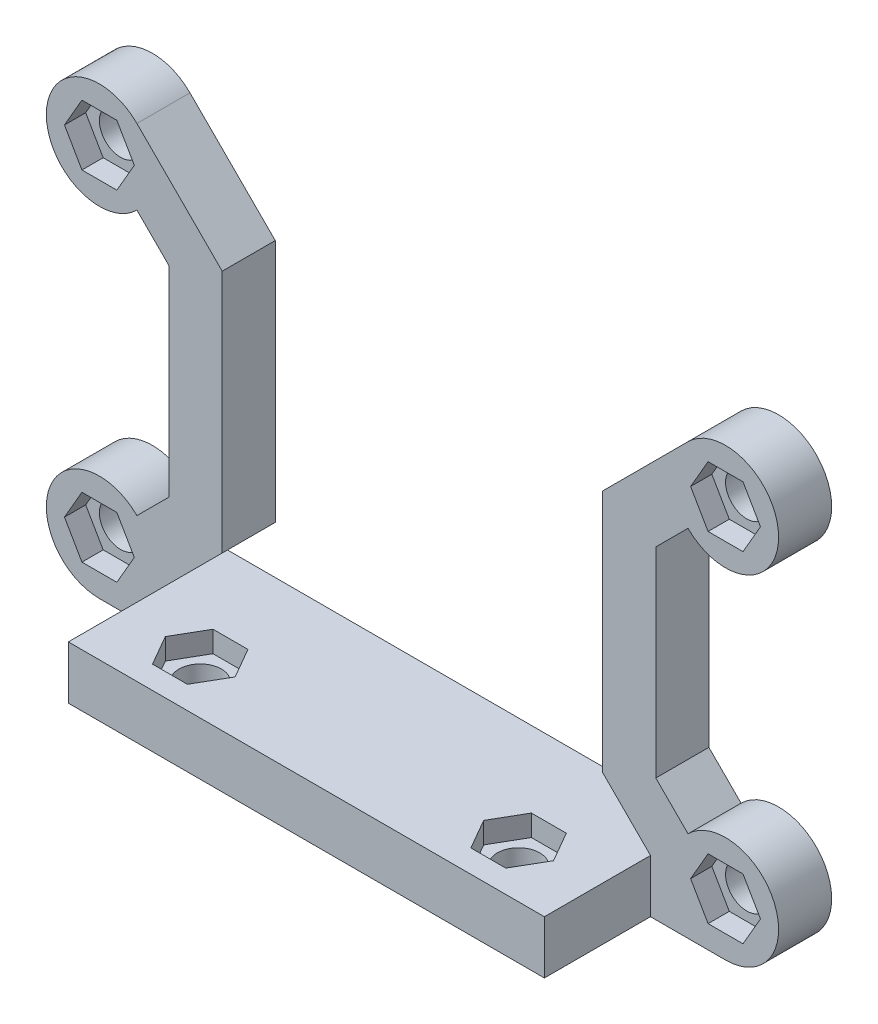
SolidWorks part; units mm, degrees
ref_plane "Plan de face" through (0, 0, 0) normal (0, 0, 1) x (1, 0, 0)
ref_plane "Plan de dessus" through (0, 0, 0) normal (0, 1, 0) x (1, 0, 0)
ref_plane "Plan de droite" through (0, 0, 0) normal (1, 0, 0) x (0, 0, -1)
sketch "Esquisse1" plane through (0, 0, 0) normal (0, 0, 1) x (1, 0, 0)
  line L0 (0, 32) -> (0, 0) construction
  line L1 (6.5711, 25.4289) -> (6.5711, 6.5711)
  line L2 (11.5711, 27.5) -> (11.5711, 4.5)
  line L3 (11.5711, 4.5) -> (3.5355, -3.5355)
  line L4 (6.5711, 6.5711) -> (3.5355, 3.5355)
  line L5 (6.5711, 25.4289) -> (3.5355, 28.4645)
  line L6 (11.5711, 27.5) -> (3.5355, 35.5355)
  line L7 (3.5355, 35.5355) -> (3.5355, 28.4645) construction
  line L8 (3.5355, 3.5355) -> (3.5355, -3.5355) construction
  line L9 (0, 32) -> (29.5, 32) construction
  line L10 (29.5, 32) -> (29.5, 0) construction
  line L11 (0, 0) -> (29.5, 0) construction
  line L12 (52.4289, 6.5711) -> (55.4645, 3.5355)
  line L13 (52.4289, 25.4289) -> (52.4289, 6.5711)
  line L14 (52.4289, 25.4289) -> (55.4645, 28.4645)
  line L15 (47.4289, 27.5) -> (55.4645, 35.5355)
  line L16 (47.4289, 27.5) -> (47.4289, 4.5)
  line L17 (47.4289, 4.5) -> (55.4645, -3.5355)
  line L18 (0, -5) -> (59, -5)
  line L19 (7.0711, 0) -> (51.9289, 0)
  circle A0 centre (0, 32) radius 2
  circle A1 centre (0, 32) radius 5 construction
  circle A2 centre (0, 0) radius 5 construction
  circle A3 centre (0, 0) radius 2
  arc A4 (3.5355, 35.5355) -> (3.5355, 28.4645) centre (0, 32) ccw
  arc A5 (3.5355, 3.5355) -> (3.5355, -3.5355) centre (0, 0) ccw
  circle A6 centre (59, 32) radius 2
  circle A7 centre (59, 0) radius 2
  arc A8 (55.4645, 35.5355) -> (55.4645, 28.4645) centre (59, 32) cw
  arc A9 (55.4645, 3.5355) -> (55.4645, -3.5355) centre (59, 0) cw
  dimension "D1" = 4
  dimension "D2" = 10
  dimension "D3" = 32
  dimension "D4" = 5
  dimension "D5" = 5
  dimension "D6" = 5
  dimension "D7" = 135
  dimension "D8" = 135
  dimension "D9" = 23
  dimension "D10" = 29.5
  dimension "D11" = 5
extrude "Boss.-Extru.1" add sketch "Esquisse1" along normal blind 5 contours L18 A9 L17 L19 L3 A5 | L4 A5 L3 L2 L6 A4 L5 L1 A0 A3 | A9 L12 L13 L14 A8 L15 L16 L17 A6 A7 region at (5.3726, 27.266, 0) region at (29.5, -2.5927, 0) region at (57.2594, -4.2023, 0)
sketch "Esquisse2" plane through (0, -5, 0) normal (0, -1, 0) x (1, 0, 0)
  line L0 (0, 5) -> (59, 5) construction
  line L1 (9.5, 5) -> (49.5, 5)
  line L2 (9.5, 5) -> (9.5, 15) construction
  line L3 (9.5, 15) -> (49.5, 15)
  line L4 (49.5, 5) -> (49.5, 15) construction
  line L5 (0, 0) -> (59, 0) construction
  line L6 (9.5, 15) -> (19.5, 5) construction
  line L7 (49.5, 15) -> (39.5, 5) construction
  line L8 (29.5, 15) -> (29.5, 5) construction
  line L9 (9.5, 5) -> (7.0711, 5)
  line L10 (9.5, 5) -> (9.5, 15) construction
  line L11 (9.5, 15) -> (7.0711, 15)
  line L12 (7.0711, 5) -> (7.0711, 15)
  line L14 (49.5, 15) -> (51.9289, 15)
  line L15 (49.5, 5) -> (51.9289, 5)
  line L16 (51.9289, 5) -> (51.9289, 15)
  circle A0 centre (14.5, 10) radius 2
  circle A1 centre (44.5, 10) radius 2
  point P8 (29.5, 0)
  point P9 (29.5, 15)
  point P16 (14.5, 10)
  point P17 (44.5, 10)
  dimension "D3" = 4
  dimension "D1" = 10
  dimension "D2" = 40
  dimension "D4" = 10
  dimension "D5" = 10
extrude "Boss.-Extru.2" add sketch "Esquisse2" against normal blind 5
sketch "Esquisse3" plane through (0, 0, 0) normal (0, 1, 0) x (1, 0, 0)
  line L0 (46.1454, -7.15) -> (42.8546, -7.15)
  line L1 (42.8546, -7.15) -> (41.2091, -10)
  line L2 (41.2091, -10) -> (42.8546, -12.85)
  line L3 (42.8546, -12.85) -> (46.1454, -12.85)
  line L4 (46.1454, -12.85) -> (47.7909, -10)
  line L5 (47.7909, -10) -> (46.1454, -7.15)
  line L7 (47.7909, -10) -> (41.2091, -10) construction
  line L8 (16.1454, -7.15) -> (12.8546, -7.15)
  line L9 (12.8546, -7.15) -> (11.2091, -10)
  line L10 (11.2091, -10) -> (12.8546, -12.85)
  line L11 (12.8546, -12.85) -> (16.1454, -12.85)
  line L12 (16.1454, -12.85) -> (17.7909, -10)
  line L13 (17.7909, -10) -> (16.1454, -7.15)
  line L14 (17.7909, -10) -> (11.2091, -10) construction
  point P2 (44.5, -10)
  point P7 (14.5, -10)
  point P12 (21.173, -21.4173)
  point P17 (14.5, -10)
  point P19 (44.5, -10)
  dimension "D1" = 120
  dimension "D2" = 5.7
  dimension "D3" = 120
  dimension "D4" = 5.7
extrude "Enlèv. mat.-Extru.1" cut sketch "Esquisse3" against normal blind 2
sketch "Esquisse4" plane through (0, 0, 5) normal (0, 0, 1) x (1, 0, 0)
  line L0 (1.6454, 34.85) -> (-1.6454, 34.85)
  line L1 (-1.6454, 34.85) -> (-3.2909, 32)
  line L2 (-3.2909, 32) -> (-1.6454, 29.15)
  line L3 (-1.6454, 29.15) -> (1.6454, 29.15)
  line L4 (1.6454, 29.15) -> (3.2909, 32)
  line L5 (3.2909, 32) -> (1.6454, 34.85)
  line L6 (3.2909, 32) -> (-3.2909, 32) construction
  line L7 (60.6454, 34.85) -> (57.3546, 34.85)
  line L8 (57.3546, 34.85) -> (55.7091, 32)
  line L9 (55.7091, 32) -> (57.3546, 29.15)
  line L10 (57.3546, 29.15) -> (60.6454, 29.15)
  line L11 (60.6454, 29.15) -> (62.2909, 32)
  line L12 (62.2909, 32) -> (60.6454, 34.85)
  line L13 (62.2909, 32) -> (55.7091, 32) construction
  line L14 (60.6454, 2.85) -> (57.3546, 2.85)
  line L15 (57.3546, 2.85) -> (55.7091, 0)
  line L16 (55.7091, 0) -> (57.3546, -2.85)
  line L17 (57.3546, -2.85) -> (60.6454, -2.85)
  line L18 (60.6454, -2.85) -> (62.2909, 0)
  line L19 (62.2909, 0) -> (60.6454, 2.85)
  line L20 (62.2909, 0) -> (55.7091, 0) construction
  line L21 (1.6454, 2.85) -> (-1.6454, 2.85)
  line L22 (-1.6454, 2.85) -> (-3.2909, 0)
  line L23 (-3.2909, 0) -> (-1.6454, -2.85)
  line L24 (-1.6454, -2.85) -> (1.6454, -2.85)
  line L25 (1.6454, -2.85) -> (3.2909, 0)
  line L26 (3.2909, 0) -> (1.6454, 2.85)
  line L27 (3.2909, 0) -> (-3.2909, 0) construction
  point P0 (0, 32)
  point P7 (0, 32)
  point P8 (0, 32)
  point P9 (0, 0)
  point P11 (59, 0)
  point P13 (59, 32)
  point P15 (59, 32)
  point P23 (59, 32)
  point P24 (59, 0)
  point P31 (59, 0)
  point P32 (0, 0)
  point P39 (0, 0)
  point P40 (0, 0)
  point P41 (0, 0)
  point P42 (0, 0)
  point P43 (0, 0)
  dimension "D1" = 120
  dimension "D2" = 5.7
  dimension "D3" = 120
  dimension "D4" = 5.7
  dimension "D5" = 120
  dimension "D6" = 5.7
  dimension "D7" = 120
  dimension "D8" = 5.7
extrude "Enlèv. mat.-Extru.2" cut sketch "Esquisse4" against normal blind 2
